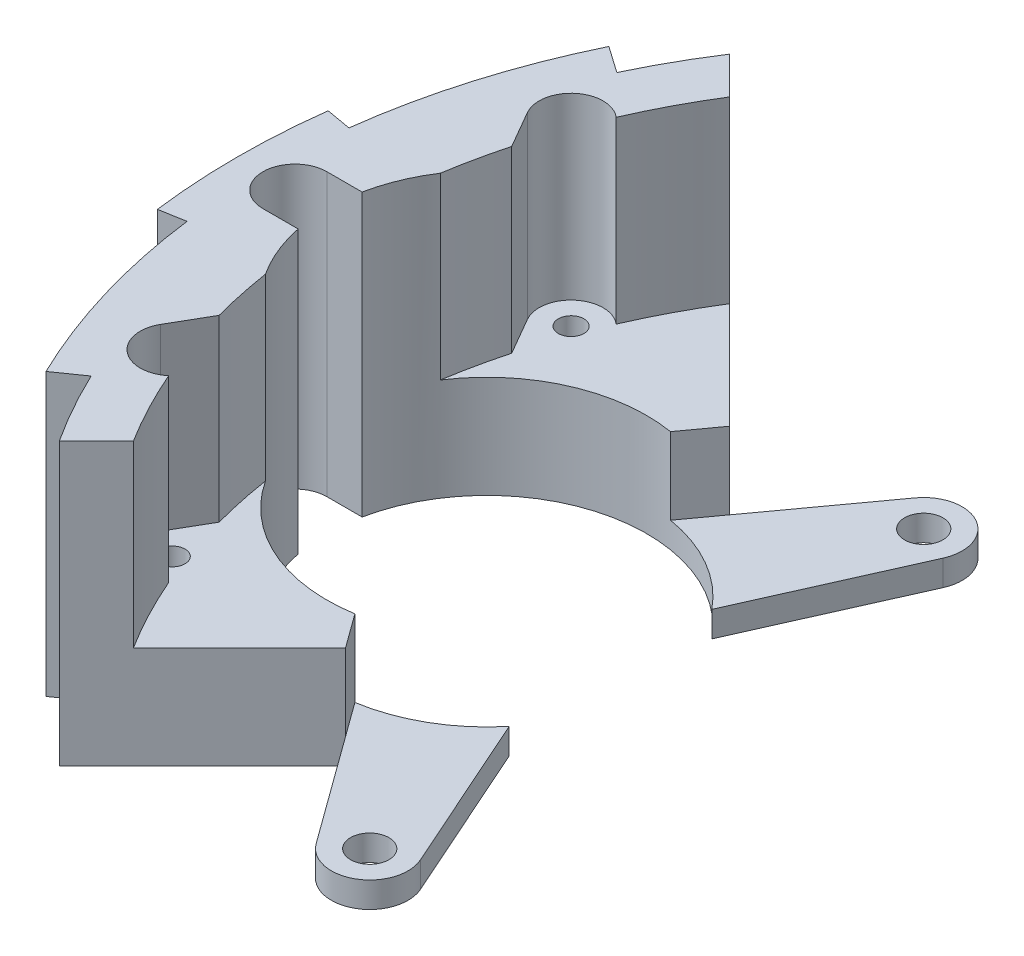
SolidWorks part; units mm, degrees
ref_plane "Front Plane" through (0, 0, 0) normal (0, 0, 1) x (1, 0, 0)
ref_plane "Top Plane" through (0, 0, 0) normal (0, 1, 0) x (1, 0, 0)
ref_plane "Right Plane" through (0, 0, 0) normal (1, 0, 0) x (0, 0, -1)
sketch "Sketch2" plane through (0, 0, 0) normal (0, 1, 0) x (1, 0, 0)
  line L0 (0, 0) -> (-15, 0) construction
  line L1 (-15, 2.5) -> (-12.2474, 2.5)
  line L2 (-15, -2.5) -> (-12.2474, -2.5)
  line L3 (0, 0) -> (33, 0) construction
  line L4 (0, 0) -> (-9, 15.5885) construction
  line L5 (0, 0) -> (12.5, 21.6506) construction
  line L6 (-11.1651, 14.3385) -> (-8.2888, 9.3566)
  line L7 (-6.8349, 16.8385) -> (-3.9587, 11.8566)
  line L8 (10.0729, 23.414) -> (2.0237, 12.3351)
  line L9 (9.6707, -7.9201) -> (15.2406, -20.4304)
  line L10 (9.6707, 7.9201) -> (15.2406, 20.4304)
  line L11 (10.0729, -23.414) -> (2.0237, -12.3351)
  line L12 (-6.8349, -16.8385) -> (-3.9587, -11.8566)
  line L13 (-11.1651, -14.3385) -> (-8.2888, -9.3566)
  line L14 (-12.4569, 21.9982) -> (-10.381, 20.5447)
  line L15 (-12.4569, -21.9982) -> (-10.381, -20.5447)
  line L16 (-10.381, 20.5447) -> (18.9598, 0) construction
  line L17 (-19.0742, 6.673) -> (-17.1021, 6.327)
  line L18 (-19.0742, -6.673) -> (-17.1021, -6.327)
  line L21 (-7.2273, 26.1871) -> (18.9598, 0) construction
  line L22 (-7.2273, 26.1871) -> (3.9598, 15)
  line L23 (-7.2273, -26.1871) -> (3.9598, -15)
  arc A0 (-12.2474, -2.5) -> (-12.2474, 2.5) centre (0, 0) ccw
  arc A2 (-12.4569, 21.9982) -> (-12.4569, -21.9982) centre (33, 0) ccw
  circle A3 centre (33, 0) radius 40 construction
  circle A4 centre (33, 0) radius 27.5 construction
  arc A5 (15.2406, 20.4304) -> (10.0729, 23.414) centre (12.5, 21.6506) ccw
  arc A6 (-6.8349, 16.8385) -> (-11.1651, 14.3385) centre (-9, 15.5885) ccw
  arc A7 (15.2406, -20.4304) -> (10.0729, -23.414) centre (12.5, -21.6506) cw
  arc A8 (-6.8349, -16.8385) -> (-11.1651, -14.3385) centre (-9, -15.5885) cw
  arc A9 (-15, 2.5) -> (-15, -2.5) centre (-15, 0) ccw
  arc A10 (-19.0742, 6.673) -> (-19.0742, -6.673) centre (33, 0) ccw
  circle A11 centre (12.5, 21.6506) radius 1.5
  circle A12 centre (12.5, -21.6506) radius 1.5
  circle A13 centre (-9, 15.5885) radius 1
  circle A14 centre (-9, -15.5885) radius 1
  arc A17 (-10.381, 20.5447) -> (-7.2273, 26.1871) centre (33, 0) cw
  arc A20 (-10.381, -20.5447) -> (-7.2273, -26.1871) centre (33, 0) ccw
  point P11 (-17.5, 0)
  point P14 (-7, 0)
  point P40 (-18.0881, 6.5)
  point P54 (0, 0)
  point P56 (0, 0)
  point P57 (0, 0)
  point P58 (-6.27, 17.7685)
  dimension "D1" = 25
  dimension "D4" = 2.5
  dimension "D6" = 80
  dimension "D7" = 55
  dimension "D8" = 18
  dimension "D12" = 5
  dimension "D13" = 6
  dimension "D18" = 105
  dimension "D20" = 3
  dimension "D21" = 3
  dimension "D22" = 2
  dimension "D26" = 50.5
  dimension "D28" = 48
  dimension "D3" = 15
  dimension "D5" = 7
  dimension "D9" = 25
  dimension "D10" = 60
  dimension "D11" = 120
  dimension "D14" = 6
  dimension "D15" = 6
  dimension "D16" = 35
  dimension "D17" = 15
  dimension "D19" = 4
  dimension "D27" = 45
  dimension "D29" = 33
extrude "Boss-Extrude1" add sketch "Sketch2" along normal blind 8 contours L15 A20 L23 L11 A0 L12 A8 L13 L2 A9 A2 | A8 L12 A0 L13 A14 | A17 L14 A2 A9 L1 A0 L6 A6 L7 L8 L22 | L7 A6 L6 A0 A13 | L17 A10 L18 A2 region at (-17.0072, 0, -2.0072) region at (-18.3715, 0, 0) region at (-17.0072, 0, 2.0072) region at (-8.0238, 0, -13.8976) region at (-8.0238, 0, 13.8976)
extrude "Boss-Extrude9" add sketch "Sketch2<5>" along normal blind 2 contours A7 L9 A0 L11 A12 | L10 A5 L8 A0 A11 region at (9.4405, 0, -16.3513) region at (9.4405, 0, 16.3513)
sketch "Sketch2<5>" plane through (0, 0, 0) normal (0, 1, 0) x (1, 0, 0) same geometry as "Sketch2"
ref_plane "Plane1" through (0, 8, 0) normal (0, 1, 0) x (1, 0, 0)
extrude "Boss-Extrude6" add sketch "Sketch2<4>" along normal blind 2 contours A7 L9 A0 L11 A12 | L10 A5 L8 A0 A11 region at (9.4405, 0, -16.3513) region at (9.4405, 0, 16.3513)
sketch "Sketch2<4>" plane through (0, 0, 0) normal (0, 1, 0) x (1, 0, 0) same geometry as "Sketch2"
sketch "Sketch5" plane through (0, 8, 0) normal (0, 1, 0) x (1, 0, 0)
  line L0 (0, 0) -> (-15, 0) construction
  line L1 (-15, 2.5) -> (-12.2474, 2.5)
  line L2 (-15, -2.5) -> (-12.2474, -2.5)
  line L3 (0, 0) -> (33, 0) construction
  line L4 (0, 0) -> (-9, 15.5885) construction
  line L5 (0, 0) -> (12.5, 21.6506) construction
  line L6 (-11.1651, 14.3385) -> (-8.2888, 9.3566)
  line L7 (-6.8349, 16.8385) -> (-3.9587, 11.8566)
  line L8 (10.0729, 23.414) -> (2.0237, 12.3351)
  line L9 (9.6707, -7.9201) -> (15.2406, -20.4304)
  line L10 (9.6707, 7.9201) -> (15.2406, 20.4304)
  line L11 (10.0729, -23.414) -> (2.0237, -12.3351)
  line L12 (-6.8349, -16.8385) -> (-3.9587, -11.8566)
  line L13 (-11.1651, -14.3385) -> (-8.2888, -9.3566)
  line L14 (-12.4569, 21.9982) -> (-10.381, 20.5447)
  line L15 (-12.4569, -21.9982) -> (-10.381, -20.5447)
  line L16 (-10.381, 20.5447) -> (18.9598, 0) construction
  line L17 (-19.0742, 6.673) -> (-17.1021, 6.327)
  line L18 (-19.0742, -6.673) -> (-17.1021, -6.327)
  line L21 (-7.2273, 26.1871) -> (18.9598, 0) construction
  line L22 (-7.2273, 26.1871) -> (3.9598, 15)
  line L23 (-7.2273, -26.1871) -> (3.9598, -15)
  arc A0 (-12.2474, -2.5) -> (-12.2474, 2.5) centre (0, 0) ccw
  arc A2 (-12.4569, 21.9982) -> (-12.4569, -21.9982) centre (33, 0) ccw
  circle A3 centre (33, 0) radius 40 construction
  circle A4 centre (33, 0) radius 27.5 construction
  arc A5 (15.2406, 20.4304) -> (10.0729, 23.414) centre (12.5, 21.6506) ccw
  arc A6 (-6.8349, 16.8385) -> (-11.1651, 14.3385) centre (-9, 15.5885) ccw
  arc A7 (15.2406, -20.4304) -> (10.0729, -23.414) centre (12.5, -21.6506) cw
  arc A8 (-6.8349, -16.8385) -> (-11.1651, -14.3385) centre (-9, -15.5885) cw
  arc A9 (-15, 2.5) -> (-15, -2.5) centre (-15, 0) ccw
  arc A10 (-19.0742, 6.673) -> (-19.0742, -6.673) centre (33, 0) ccw
  circle A11 centre (12.5, 21.6506) radius 1.5
  circle A12 centre (12.5, -21.6506) radius 1.5
  circle A13 centre (-9, 15.5885) radius 1
  circle A14 centre (-9, -15.5885) radius 1
  arc A17 (-10.381, 20.5447) -> (-7.2273, 26.1871) centre (33, 0) cw
  arc A20 (-10.381, -20.5447) -> (-7.2273, -26.1871) centre (33, 0) ccw
  point P11 (-17.5, 0)
  point P14 (-7, 0)
  point P54 (0, 0)
  point P56 (0, 0)
  point P57 (0, 0)
  point P58 (-6.27, 17.7685)
extrude "Boss-Extrude7" add sketch "Sketch5" along normal blind 14 contours A17 L14 A2 A9 L1 A0 L6 A6 L7 L8 L22 | L15 A20 L23 L11 A0 L12 A8 L13 L2 A9 A2 | L17 A10 L18 A2 region at (-17.0072, 8, -2.0072) region at (-18.3715, 8, 0) region at (-17.0072, 8, 2.0072)
sketch "Sketch7" plane through (0, 22, 0) normal (0, 1, 0) x (1, 0, 0)
  line L0 (0, 0) -> (33, 0) construction
  circle A0 centre (33, 0) radius 44
  dimension "D2" = 88
  dimension "D1" = 33
extrude "Cut-Extrude2" cut sketch "Sketch7" against normal blind 14
ref_axis "TyreCentre" through (33, 0, 0) along (0, 1, 0)
sketch "Sketch9" [suppressed] plane through (0, 0, 0) normal (0, -1, 0) x (1, 0, 0)
  line L0 (-8.2888, 9.3566) -> (-11.1651, 14.3385)
  line L1 (-3.9587, 11.8566) -> (-6.8349, 16.8385)
  line L2 (0, 0) -> (15, 0) construction
  line L3 (-12.3904, 13.0567) -> (0, 0)
  line L4 (0, 0) -> (-5.1123, 17.2588)
  line L5 (-12.5467, 10.7159) -> (0, 0)
  line L6 (0, 0) -> (-3.0069, 16.2237)
  line L7 (-4.6863, 15.8205) -> (-5.4557, 17.1533)
  line L8 (-11.3579, 11.9687) -> (-12.1273, 13.3014)
  circle A0 centre (0, 0) radius 15
  arc A1 (-11.1651, 14.3385) -> (-6.8349, 16.8385) centre (-9, 15.5885) cw
  arc A2 (-6.8349, 16.8385) -> (-11.1651, 14.3385) centre (-9, 15.5885) ccw construction
  arc A3 (-12.3904, 13.0567) -> (-5.1123, 17.2588) centre (0, 0) cw
  arc A4 (-11.3579, 11.9687) -> (-4.6863, 15.8205) centre (0, 0) cw
  arc A5 (-12.5467, 10.7159) -> (-11.3579, 11.9687) centre (0, 0) cw
  arc A6 (-4.6863, 15.8205) -> (-3.0069, 16.2237) centre (0, 0) cw
  point P20 (-9, 15.5885)
  dimension "D1" = 30
  dimension "D2" = 16.5
  dimension "D3" = 27
  dimension "D4" = 6
  dimension "D5" = 6
extrude "Boss-Extrude8" [suppressed] add sketch "Sketch9" along normal blind 2 contours L8 A4 L0 A3 | A4 L3 A0 L0 | A5 L5 A0 L3 | A6 L4 A0 L6 | A4 L1 A0 L4 | L1 A4 L7 A3
mirror "Mirror3" [suppressed] about plane through (0, 0, 0) normal (0, 0, 1)
